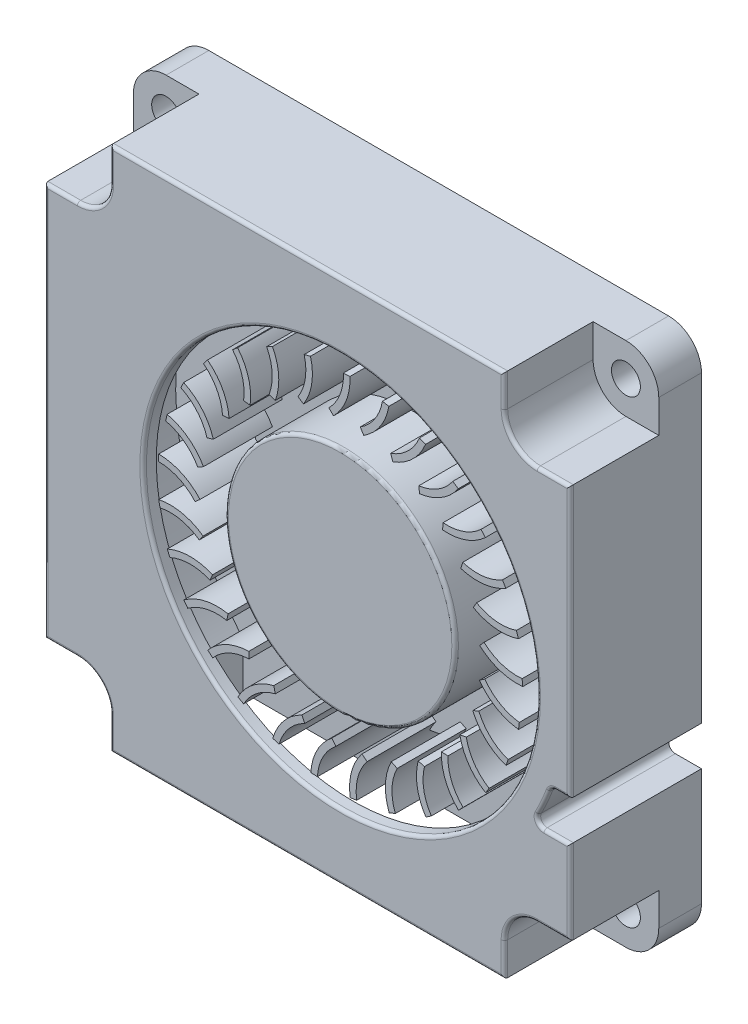
SolidWorks part; units mm, degrees
ref_plane "Front Plane" through (0, 0, 0) normal (0, 0, 1) x (1, 0, 0)
ref_plane "Top Plane" through (0, 0, 0) normal (0, 1, 0) x (1, 0, 0)
ref_plane "Right Plane" through (0, 0, 0) normal (1, 0, 0) x (0, 0, -1)
ref_axis "Axis1" through (0, 0, -5.5) along (0, 0, 1)
sketch "Sketch1" plane through (0, 0, 0) normal (0, 0, 1) x (1, 0, 0)
  line L1 (-20, 20) -> (20, 20)
  line L2 (-20, 20) -> (-20, -20)
  line L3 (-20, -20) -> (20, -20)
  line L4 (20, 20) -> (20, -20)
  line L5 (-20, 20) -> (20, -20) construction
  line L6 (-20, -20) -> (20, 20) construction
  point P0 (0, 0)
  dimension "D1" = 40
extrude "Boss-Extrude1" add sketch "Sketch1" along normal mid plane 10
sketch "Sketch3" plane through (0, 0, 5) normal (0, 0, 1) x (1, 0, 0)
  line L1 (20, 20) -> (15, 20)
  line L2 (20, 20) -> (20, 15)
  line L3 (20, 15) -> (15, 15)
  line L4 (15, 20) -> (15, 15)
  dimension "D1" = 5
extrude "Cut-Extrude1" cut sketch "Sketch3" against normal blind 6.75
fillet "Fillet1" radius 2.5 2 edges at (20, 20, -3.375) (15, 15, 1.625)
sketch "Sketch4" plane through (0, 0, -1.75) normal (0, 0, 1) x (1, 0, 0)
  line L1 (-17.5, 17.5) -> (17.5, 17.5) construction
  line L2 (-17.5, 17.5) -> (-17.5, -17.5) construction
  line L3 (-17.5, -17.5) -> (17.5, -17.5) construction
  line L4 (17.5, 17.5) -> (17.5, -17.5) construction
  line L5 (-17.5, 17.5) -> (17.5, -17.5) construction
  line L6 (-17.5, -17.5) -> (17.5, 17.5) construction
  circle A0 centre (17.5, 17.5) radius 1.1
  circle A1 centre (-17.5, 17.5) radius 1.1
  circle A2 centre (-17.5, -17.5) radius 1.1
  circle A3 centre (17.5, -17.5) radius 1.1
  point P0 (0, 0)
  dimension "D1" = 2.2
  dimension "D2" = 35
extrude "Cut-Extrude2" cut sketch "Sketch4" against normal through all
pattern_circular "CirPattern1" count 4 over 360 about axis through (0, 0, -5.5) along (0, 0, 1) of "Cut-Extrude1", "Cut-Extrude2", "Fillet1"
sketch "Sketch2" plane through (0, 0, 5) normal (0, 0, 1) x (1, 0, 0)
  line L0 (0, 0) -> (2.5, 0) construction
  line L3 (20, -15) -> (20, 15) construction
  circle A0 centre (2.5, 0) radius 15
  circle A1 centre (2.5, 0) radius 13.75
  dimension "D1" = 30
  dimension "D3" = 27.5
  dimension "D2" = 17.5
sketch "Sketch5" plane through (0, 0, 5) normal (0, 0, 1) x (1, 0, 0)
  line L0 (20, -8.6) -> (18.0126, -8.6)
  line L1 (20, -15) -> (20, 15) construction
  line L3 (18.9024, -5.6) -> (20, -5.6)
  line L4 (20, -8.6) -> (20, -5.6)
  line L6 (15, -20) -> (17.5, -20) construction
  arc A0 (17.5694, -7.8686) -> (18.4338, -5.9257) centre (2.5, 0) ccw
  arc A1 (18.0126, -8.6) -> (17.5694, -7.8686) centre (18.0126, -8.1) cw
  arc A2 (18.4338, -5.9257) -> (18.9024, -5.6) centre (18.9024, -6.1) cw
  dimension "D3" = 17
  dimension "D4" = 0.5
  dimension "D1" = 11.4
  dimension "D2" = 3
extrude "Cut-Extrude3" cut sketch "Sketch5" against normal through all
sketch "Sketch8" plane through (0, 0, 5) normal (0, 0, 1) x (1, 0, 0)
  line L0 (13.9, -20) -> (13.9, -9.7488)
  line L3 (-15, -20) -> (15, -20) construction
  line L4 (15, -17.5) -> (15, -20) construction
  line L5 (20, 0) -> (18.9, 0) construction
  line L6 (20, -5.6) -> (20, 15) construction
  line L7 (0, 20) -> (0, 18.9) construction
  line L8 (15, 20) -> (-15, 20) construction
  line L9 (-20, 0) -> (-18.9, 0) construction
  line L10 (-20, 15) -> (-20, -15) construction
  line L11 (-13.9, -20) -> (-13.9, -16.5)
  line L12 (-15, -20) -> (-15, -17.5) construction
  line L15 (-13.9, -20) -> (13.9, -20)
  circle A2 centre (2.5, 0) radius 15 construction
  arc A3 (13.9, -9.7488) -> (18.9, 0) centre (3.7564, 1.6103) ccw
  arc A4 (18.9, 0) -> (0, 18.9) centre (1.8165, 1.8165) ccw
  arc A5 (0, 18.9) -> (-18.9, 0) centre (2.2488, -2.2488) ccw
  arc A6 (-18.9, 0) -> (-13.9, -16.5) centre (3.1039, -2.3397) ccw
  arc A11 (15, 17.5) -> (17.5, 15) centre (17.5, 17.5) ccw construction
  dimension "D5" = 2.5
  dimension "D1" = 1.1
  dimension "D2" = 1.1
  dimension "D3" = 1.1
  dimension "D4" = 3.5
extrude "Cut-Extrude5" cut sketch "Sketch8" against normal offset from surface (8 mm away) 1 from offset 1 up to face at (18.6, 17.5, -5) offset against normal yes
extrude "Cut-Extrude6" cut sketch "Sketch2" against normal up to next contours A0
sketch "Sketch11" plane through (0, 0, -4) normal (0, 0, 1) x (1, 0, 0)
  circle A0 centre (2.5, 0) radius 11.75
  dimension "D1" = 23.5
extrude "Boss-Extrude2" add sketch "Sketch11" along normal blind 3.75
sketch "Sketch12" plane through (0, 0, -0.25) normal (0, 0, 1) x (1, 0, 0)
  line L0 (2.5, 11.75) -> (2.5, 0) construction
  line L1 (2.9896, 13.8664) -> (1.8122, 10.8371) construction
  circle A0 centre (2.5, 0) radius 11.75 construction
  circle A1 centre (2.5, 0) radius 11.75 construction
  arc A2 (1.8122, 10.8371) -> (2.9896, 13.8664) centre (-1.0058, 13.6759) ccw
  dimension "D1" = 3.25
  dimension "D3" = 13.875
extrude "Extrude-Thin1" add sketch "Sketch12" along normal up to surface (5.25 mm away) and the other way offset from surface 1 thin up to face at (17.5, 0, 5) other way up to face at (14.25, 0, -4) thin type mid plane wall 0.5
pattern_circular "CirPattern2" count 29 over 360 about axis through (2.5, 0, -0.25) along (0, 0, -1) of "Extrude-Thin1"
sketch "Sketch13" plane through (0, 0, -0.25) normal (0, 0, 1) x (1, 0, 0)
  circle A0 centre (2.5, 0) radius 8.75
  dimension "D1" = 17.5
extrude "Boss-Extrude3" add sketch "Sketch13" along normal up to surface (5.25 mm away) up to face at (17.5, 0, 5)
fillet "Fillet2" radius 0.25 24 edges at (20, -11.8, 5) (18.75, -15, 5) (15.7322, -15.7322, 5) (15, -18.75, 5) (0, -20, 5) (-15, -18.75, 5) (-15.7322, -15.7322, 5) (-18.75, -15, 5) (-20, 0, 5) (-18.75, 15, 5) (-15.7322, 15.7322, 5) (-15, 18.75, 5) (0, 20, 5) (15, 18.75, 5) (15.7322, 15.7322, 5) (18.75, 15, 5) (20, 4.7, 5) (19.4512, -5.6, 5) (18.6171, -5.6894, 5) (18.032, -6.9107, 5) (17.585, -8.3591, 5) (19.0063, -8.6, 5) (17.5, 0, 5) (11.25, 0, 5)
